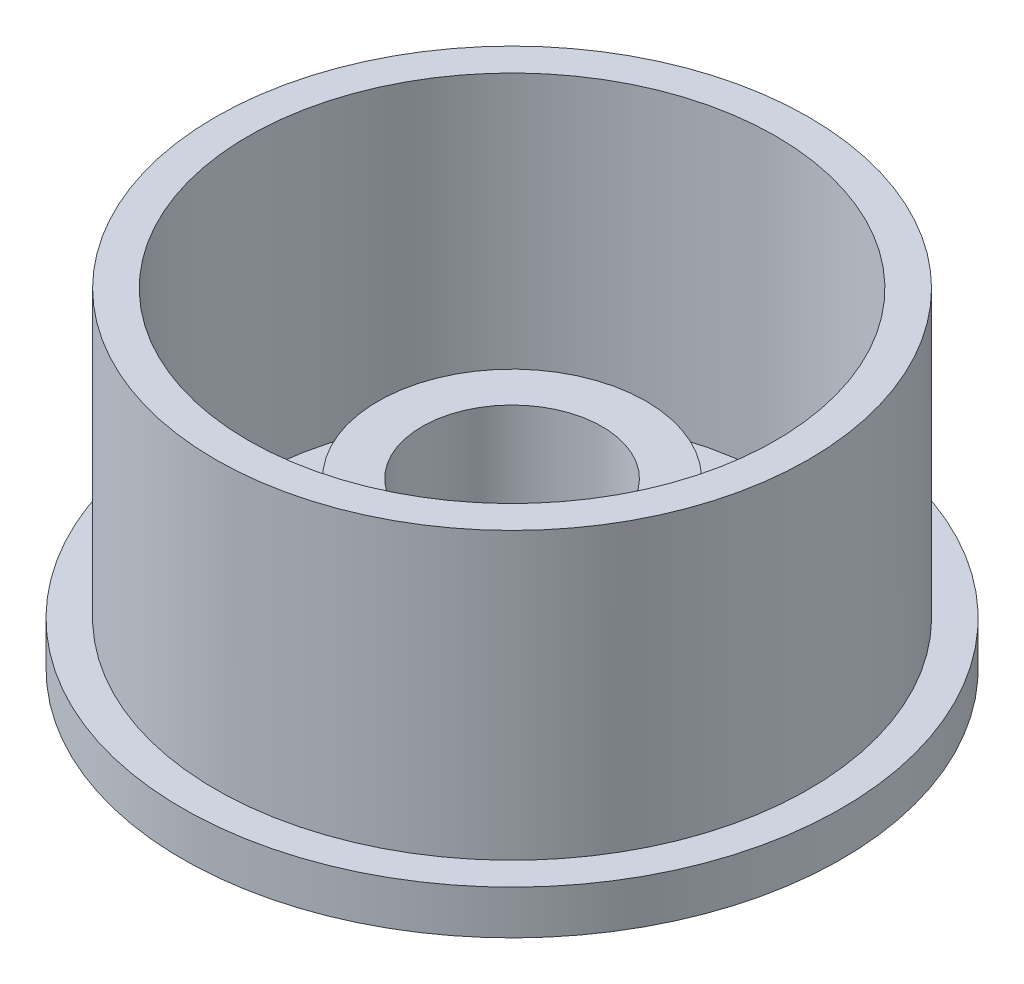
SolidWorks part; units mm, degrees
ref_plane "Front Plane" through (0, 0, 0) normal (0, 0, 1) x (1, 0, 0)
ref_plane "Top Plane" through (0, 0, 0) normal (0, 1, 0) x (1, 0, 0)
ref_plane "Right Plane" through (0, 0, 0) normal (1, 0, 0) x (0, 0, -1)
sketch "Sketch1" plane through (0, 0, 0) normal (0, 1, 0) x (1, 0, 0)
  circle A0 centre (0, 0) radius 13.5
  dimension "D1" = 27
extrude "Boss-Extrude1" add sketch "Sketch1" along normal blind 15
shell "Shell1" thickness 1.5 removed face at (0, 15, 13.5)
sketch "Sketch2" plane through (0, 1.5, 0) normal (0, 1, 0) x (1, 0, 0)
  circle A0 centre (0, 0) radius 4.1
  dimension "D1" = 8.2
extrude "Cut-Extrude1" cut sketch "Sketch2" against normal blind 20
sketch "Sketch3" plane through (0, 1.5, 0) normal (0, 1, 0) x (1, 0, 0)
  circle A0 centre (0, 0) radius 4.1
  circle A1 centre (0, 0) radius 6.1
  circle A2 centre (0, 0) radius 4.1 construction
  dimension "D1" = 2
extrude "Boss-Extrude2" add sketch "Sketch3" along normal offset from surface (6 mm away) 7.5 up to face at (0, 0, 4.1)
sketch "Sketch4" plane through (0, 0, 0) normal (0, -1, 0) x (1, 0, 0)
  circle A0 centre (0, 0) radius 12.5
  circle A1 centre (0, 0) radius 15
  circle A3 centre (0, 0) radius 13.5 construction
  dimension "D1" = 1.5
  dimension "D2" = 1
extrude "Boss-Extrude3" add sketch "Sketch4" against normal blind 2 separate body
combine bodies "Combine1" operation type add bodies to combine 103 104
